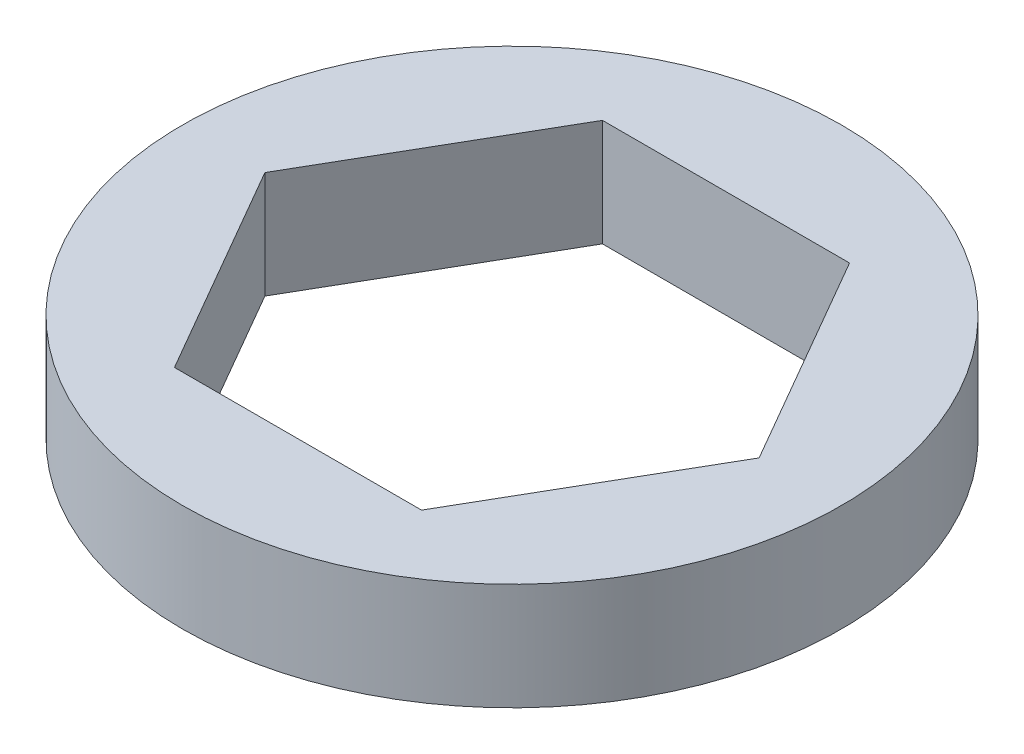
SolidWorks part; units mm, degrees
material "Nylon 101"
ref_plane "Front Plane" through (0, 0, 0) normal (0, 0, 1) x (1, 0, 0)
ref_plane "Top Plane" through (0, 0, 0) normal (0, 1, 0) x (1, 0, 0)
ref_plane "Right Plane" through (0, 0, 0) normal (1, 0, 0) x (0, 0, -1)
sketch "Sketch1" plane through (0, 0, 0) normal (0, 1, 0) x (1, 0, 0)
  line L1 (-3.6662, 6.35) -> (-7.3323, 0)
  line L2 (-7.3323, 0) -> (-3.6662, -6.35)
  line L3 (-3.6662, -6.35) -> (3.6662, -6.35)
  line L4 (3.6662, -6.35) -> (7.3323, 0)
  line L5 (7.3323, 0) -> (3.6662, 6.35)
  line L6 (3.6662, 6.35) -> (-3.6662, 6.35)
  circle A0 centre (0, 0) radius 9.779
  circle A1 centre (0, 0) radius 6.35 construction
  dimension "D1" = 12.7
  dimension "D2" = 19.558
extrude "Boss-Extrude1" add sketch "Sketch1" against normal mid plane 3.175
equation "\"Length\"= 0.125"
equation "\"D1@Boss-Extrude1\"=\"Length\""
